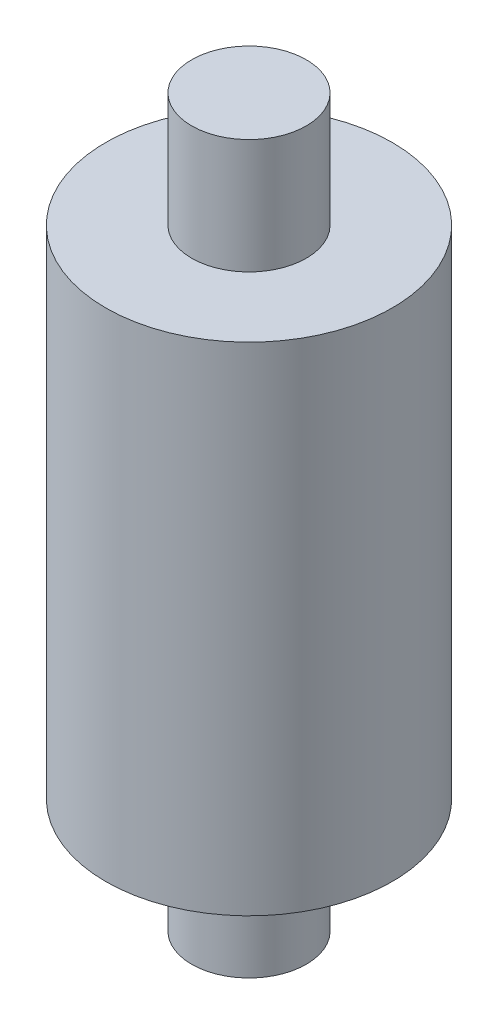
SolidWorks part; units mm, degrees
ref_plane "Front Plane" through (0, 0, 0) normal (0, 0, 1) x (1, 0, 0)
ref_plane "Top Plane" through (0, 0, 0) normal (0, 1, 0) x (1, 0, 0)
ref_plane "Right Plane" through (0, 0, 0) normal (1, 0, 0) x (0, 0, -1)
sketch "Sketch1" plane through (0, 0, 0) normal (0, 1, 0) x (1, 0, 0)
  circle A0 centre (0, 0) radius 3
  circle A1 centre (0, 0) radius 7.5
extrude "Boss-Extrude1" add sketch "Sketch1" along normal mid plane 38 contours A0
extrude "Boss-Extrude2" add sketch "Sketch1<3>" along normal mid plane 26
sketch "Sketch1<3>" plane through (0, 0, 0) normal (0, 1, 0) x (1, 0, 0) same geometry as "Sketch1"
